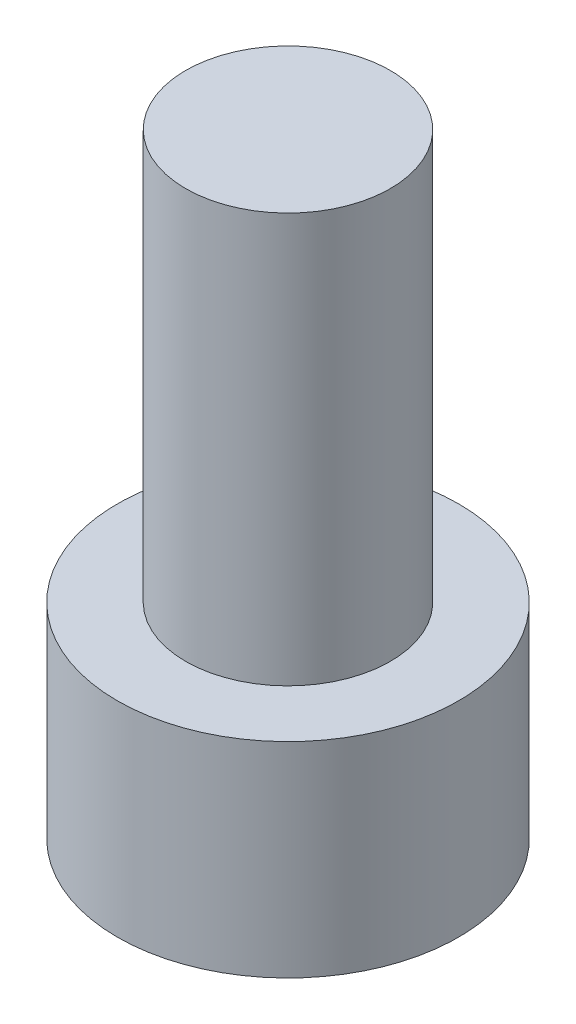
SolidWorks part; units mm, degrees
ref_plane "Front Plane" through (0, 0, 0) normal (0, 0, 1) x (1, 0, 0)
ref_plane "Top Plane" through (0, 0, 0) normal (0, 1, 0) x (1, 0, 0)
ref_plane "Right Plane" through (0, 0, 0) normal (1, 0, 0) x (0, 0, -1)
sketch "Sketch1" plane through (0, 0, 0) normal (0, 1, 0) x (1, 0, 0)
  circle A0 centre (0, 0) radius 2.5
  circle A1 centre (0, 0) radius 1.5
  dimension "D1" = 5
  dimension "D2" = 3
extrude "Boss-Extrude1" add sketch "Sketch1" along normal blind 3 contours A0
extrude "Boss-Extrude2" add sketch "Sketch1<3>" along normal blind 9 contours A1
sketch "Sketch1<3>" plane through (0, 0, 0) normal (0, 1, 0) x (1, 0, 0) same geometry as "Sketch1"
